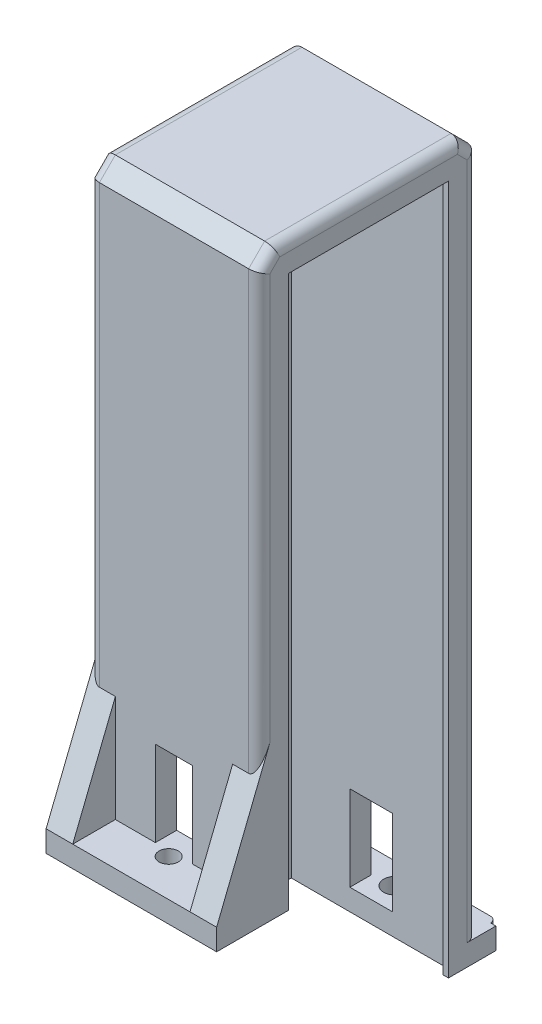
SolidWorks part; units mm, degrees
ref_plane "Płaszczyzna przednia" through (0, 0, 0) normal (0, 0, 1) x (1, 0, 0)
ref_plane "Płaszczyzna górna" through (0, 0, 0) normal (0, 1, 0) x (1, 0, 0)
ref_plane "Płaszczyzna prawa" through (0, 0, 0) normal (1, 0, 0) x (0, 0, -1)
sketch "Sketch1" plane through (0, 0, 0) normal (0, 0, 1) x (1, 0, 0)
  line L1 (0, 0) -> (30, 0)
  line L2 (0, 0) -> (0, 105)
  line L3 (0, 105) -> (30, 105)
  line L4 (30, 0) -> (30, 105)
  dimension "D1" = 105
  dimension "D2" = 30
extrude "Boss-Extrude1" add sketch "Sketch1" along normal blind 4
sketch "Sketch2" plane through (0, 0, 0) normal (0, -1, 0) x (1, 0, 0)
  line L0 (30, 4) -> (30, 0) construction
  line L1 (0, 0) -> (30, 0)
  line L2 (0, 0) -> (0, 12)
  line L3 (0, 12) -> (30, 12)
  line L4 (30, 0) -> (30, 12)
  circle A0 centre (15, 5) radius 1.8
  circle A1 centre (15, 5) radius 3.25 construction
  dimension "D2" = 3.6
  dimension "D3" = 6.5
  dimension "D1" = 12
  dimension "D4" = 5
extrude "Boss-Extrude2" add sketch "Sketch2" against normal blind 4
sketch "Sketch3" plane through (0, 0, 4) normal (0, 0, 1) x (1, 0, 0)
  line L0 (30, 4) -> (0, 4) construction
  line L1 (11.5, 4) -> (18.5, 4)
  line L2 (11.5, 4) -> (11.5, 20)
  line L3 (11.5, 20) -> (18.5, 20)
  line L4 (18.5, 4) -> (18.5, 20)
  line L5 (0, 33.7834) -> (11.5, 33.7834) construction
  line L6 (0, 105) -> (0, 4) construction
  line L7 (18.5, 31.2879) -> (30, 31.2879) construction
  line L8 (30, 4) -> (30, 105) construction
  dimension "D1" = 16
  dimension "D2" = 7
extrude "Cut-Extrude1" cut sketch "Sketch3" against normal through all
sketch "Sketch4" plane through (0, 0, 0) normal (-1, 0, 0) x (0, 0, 1)
  line L0 (12, 4) -> (0, 34)
  line L1 (0, 105) -> (0, 0) construction
  line L2 (0, 34) -> (0, 4)
  line L3 (12, 4) -> (0, 4)
  dimension "D1" = 30
extrude "Boss-Extrude3" add sketch "Sketch4" against normal blind 4
extrude "Boss-Extrude4" add sketch "Sketch4<2>" along normal blind 4 from surface starting at face at (30, 36.3333, 5.3333)
sketch "Sketch4<2>" plane through (0, 0, 0) normal (-1, 0, 0) x (0, 0, 1) same geometry as "Sketch4"
sketch "Sketch5" plane through (0, 105, 0) normal (0, 1, 0) x (1, 0, 0)
  line L0 (30, -4) -> (30, 0) construction
  line L1 (0, -4) -> (30, -4)
  line L2 (0, -4) -> (0, 37)
  line L3 (0, 37) -> (30, 37)
  line L4 (30, -4) -> (30, 37)
  dimension "D1" = 41
extrude "Boss-Extrude5" add sketch "Sketch5" along normal blind 4
sketch "Sketch6" plane through (0, 0, -37) normal (0, 0, -1) x (-1, 0, 0)
  line L0 (0, 109) -> (0, 105) construction
  line L1 (-30, 109) -> (0, 109)
  line L2 (-30, 109) -> (-30, -26)
  line L3 (-30, -26) -> (0, -26)
  line L4 (0, 109) -> (0, -26)
  line L5 (-30, 105) -> (0, 105) construction
  dimension "D1" = 131
extrude "Boss-Extrude6" add sketch "Sketch6" against normal blind 4
sketch "Sketch7" plane through (0, -26, 0) normal (0, -1, 0) x (1, 0, 0)
  line L0 (30, -33) -> (30, -37) construction
  line L1 (0, -33) -> (30, -33)
  line L2 (0, -33) -> (0, -41.5)
  line L3 (0, -41.5) -> (30, -41.5)
  line L4 (30, -33) -> (30, -41.5)
  line L5 (30, -37) -> (0, -37) construction
  dimension "D1" = 4.5
extrude "Boss-Extrude7" add sketch "Sketch7" against normal blind 4
fillet "Fillet1" radius 1.1 2 edges at (30, -24, -41.5) (0, -24, -41.5)
hole_wizard "Ø4.3 (4.3) Diameter Hole1" positions "Sketch9" profile "Sketch10" hole size "Ø4.3" standard "DIN" end condition through all
sketch "Sketch9" plane through (0, -22, 0) normal (0, 1, 0) x (1, 0, 0)
  circle A0 centre (15, 37.5) radius 2.3 construction
  point P0 (15, 37.5)
sketch "Sketch10" plane through (15, -22, -37.5) normal (1, 0, 0) x (0, 0, 1)
  line L0 (0, 0) -> (0, 4)
  line L1 (0, 4) -> (2.15, 4)
  line L2 (2.15, 4) -> (2.15, 0)
  line L5 (2.15, 0) -> (0, 0)
  line L11 (0, -6.35) -> (0, 107.95) construction
  dimension "Thru Hole Dia." = 4.3
  dimension "Thru Hole Depth" = 4
sketch "Sketch11" plane through (0, -22, 0) normal (0, 1, 0) x (1, 0, 0)
  line L1 (19, 33) -> (11, 33)
  line L2 (19, 33) -> (19, 41.5)
  line L3 (19, 41.5) -> (11, 41.5)
  line L4 (11, 33) -> (11, 41.5)
  line L5 (30, 33) -> (0, 33) construction
  line L7 (1.1, 41.5) -> (28.9, 41.5) construction
  dimension "D1" = 8
extrude "Cut-Extrude2" cut sketch "Sketch11" along normal blind 16
hole_wizard "Ø3.6 (3.6) Diameter Hole1" positions "Sketch13" profile "Sketch14" hole size "Ø3.6" standard "DIN" end condition through all
sketch "Sketch13" plane through (0, 4, 0) normal (0, 1, 0) x (1, 0, 0)
  point P0 (15, -5)
sketch "Sketch14" plane through (15, 4, 5) normal (1, 0, 0) x (0, 0, 1)
  line L0 (0, 0) -> (0, 30)
  line L1 (0, 30) -> (1.8, 30)
  line L2 (1.8, 30) -> (1.8, 0)
  line L5 (1.8, 0) -> (0, 0)
  line L11 (0, -6.35) -> (0, 107.95) construction
  dimension "Thru Hole Dia." = 3.6
  dimension "Thru Hole Depth" = 30
sketch "Sketch15" plane through (0, 0, 0) normal (-1, 0, 0) x (0, 0, 1)
  line L1 (-37, 109) -> (4, 109)
  line L2 (-37, 109) -> (-37, -26)
  line L3 (-37, -26) -> (-31.5, -26)
  line L4 (4, 109) -> (4, 0)
  line L5 (-22.2605, 109) -> (-22.2605, 103.5) construction
  line L10 (-33, -26) -> (-40.4, -26) construction
  line L11 (-31.5, -26) -> (-31.5, 103.5)
  line L12 (-31.5, 103.5) -> (-1.5, 103.5)
  line L13 (-1.5, 103.5) -> (-1.5, 0)
  line L14 (12, 0) -> (0, 0) construction
  line L18 (-1.5, 0) -> (4, 0)
  dimension "D2" = 5.5
extrude "Boss-Extrude8" add sketch "Sketch15" along normal blind 1
sketch "Sketch16" plane through (0, 0, 0) normal (-1, 0, 0) x (0, 0, 1)
  line L4 (4, 24) -> (4, 0)
  line L5 (4, 0) -> (12, 0)
  line L6 (12, 0) -> (12, 4)
  line L7 (12, 4) -> (4, 24)
  line L8 (4, 24) -> (4, 0)
  line L9 (4, 0) -> (12, 0)
  line L10 (12, 0) -> (12, 4)
  line L11 (12, 4) -> (4, 24)
  line L12 (-37, -26) -> (-37, -22)
  line L13 (-37, -22) -> (-40.4, -22)
  line L14 (-40.4, -22) -> (-40.4, -26)
  line L15 (-40.4, -26) -> (-37, -26)
  line L16 (-37, -26) -> (-37, -22)
  line L17 (-37, -22) -> (-40.4, -22)
  line L18 (-40.4, -22) -> (-40.4, -26)
  line L19 (-40.4, -26) -> (-37, -26)
  dimension "D1" = 0
  dimension "D2" = 0
extrude "Boss-Extrude10" add sketch "Sketch16" along normal up to surface (1 mm away) up to face at (-1, 46.625, -16.5)
extrude "Boss-Extrude9" add sketch "Sketch15<2>" against normal blind 1 from surface starting at face at (30, 30, -15.7333)
sketch "Sketch15<2>" plane through (0, 0, 0) normal (-1, 0, 0) x (0, 0, 1) same geometry as "Sketch15"
sketch "Sketch17" plane through (30, 0, 0) normal (1, 0, 0) x (0, 0, -1)
  line L4 (-12, 0) -> (-4, 0)
  line L5 (-4, 0) -> (-4, 24)
  line L6 (-4, 24) -> (-12, 4)
  line L7 (-12, 4) -> (-12, 0)
  line L8 (-12, 0) -> (-4, 0)
  line L9 (-4, 0) -> (-4, 24)
  line L10 (-4, 24) -> (-12, 4)
  line L11 (-12, 4) -> (-12, 0)
  line L12 (40.4, -22) -> (37, -22)
  line L13 (37, -22) -> (37, -26)
  line L14 (37, -26) -> (40.4, -26)
  line L15 (40.4, -26) -> (40.4, -22)
  line L16 (40.4, -22) -> (37, -22)
  line L17 (37, -22) -> (37, -26)
  line L18 (37, -26) -> (40.4, -26)
  line L19 (40.4, -26) -> (40.4, -22)
  dimension "D1" = 0
  dimension "D2" = 0
extrude "Boss-Extrude11" add sketch "Sketch17" along normal up to surface (1 mm away) up to face at (31, 46.625, -16.5)
chamfer "Chamfer1" distance 3 angle 45 2 edges at (15, 109, -37) (15, 109, 4)
fillet "Fillet2" radius 2 10 edges at (31, 65, 4) (-1, 65, 4) (31, 42, -37) (31, 107.5, -35.5) (-1, 42, -37) (-1, 107.5, -35.5) (31, 107.5, 2.5) (-1, 107.5, 2.5) (31, 109, -16.5) (-1, 109, -16.5)
